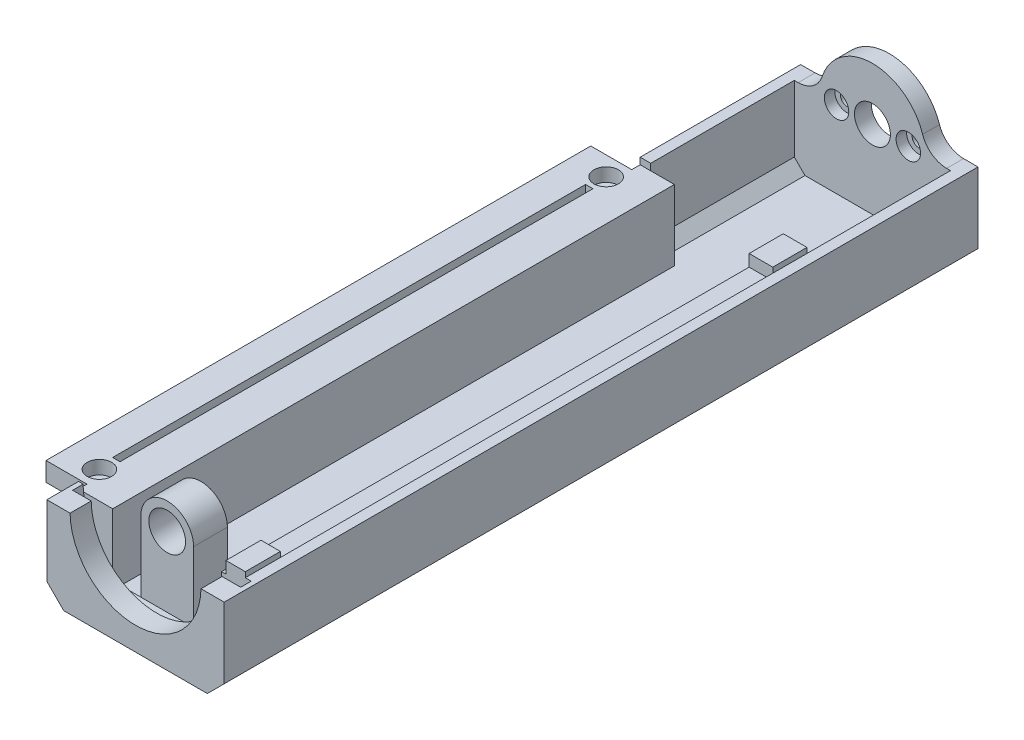
SolidWorks part; units mm, degrees
ref_plane "Front Plane" through (0, 0, 0) normal (0, 0, 1) x (1, 0, 0)
ref_plane "Top Plane" through (0, 0, 0) normal (0, 1, 0) x (1, 0, 0)
ref_plane "Right Plane" through (0, 0, 0) normal (1, 0, 0) x (0, 0, -1)
sketch "Sketch1" plane through (0, 0, 0) normal (0, 0, 1) x (1, 0, 0)
  line L0 (-21, -0.25) -> (21, -0.25)
  line L1 (-21, 21) -> (21, 21) construction
  line L2 (-21, 21) -> (-21, -21) construction
  line L3 (-21, -21) -> (21, -21) construction
  line L4 (21, 21) -> (21, -21) construction
  line L5 (-21, 21) -> (21, -21) construction
  line L6 (-21, -21) -> (21, 21) construction
  line L7 (21, -0.25) -> (21, -17)
  line L8 (21, -17) -> (17, -21)
  line L9 (17, -21) -> (-17, -21)
  line L10 (-17, -21) -> (-21, -17)
  line L11 (-21, -17) -> (-21, -0.25)
  point P0 (0, 0)
  dimension "D1" = 42
  dimension "D2" = 0.25
  dimension "D3" = 4
  dimension "D4" = 4
  dimension "D5" = 4
extrude "Boss-Extrude1" add sketch "Sketch1" along normal blind 178.5 contours L11 L0 L7 L8 L9 L10
ref_plane "Plane1" through (0, 0, 173.5) normal (0, 0, 1) x (1, 0, 0)
sketch "Sketch4" plane through (0, 0, 173.5) normal (0, 0, 1) x (1, 0, 0)
  line L6 (-18.5, -15.9645) -> (-15.9645, -18.5)
  line L7 (-15.9645, -18.5) -> (15.9645, -18.5)
  line L8 (15.9645, -18.5) -> (18.5, -15.9645)
  line L9 (18.5, -15.9645) -> (18.5, -2.75)
  line L11 (-18.5, -2.75) -> (-18.5, -15.9645)
  line L18 (-21, -17) -> (-17, -21)
  line L22 (-21, -0.25) -> (-21, -17)
  line L23 (21, -0.25) -> (-21, -0.25)
  line L24 (21, -17) -> (21, -0.25)
  line L25 (17, -21) -> (21, -17)
  line L26 (-17, -21) -> (17, -21)
  line L27 (-21, -17) -> (-17, -21) construction
  line L28 (-21, -0.25) -> (-21, -17) construction
  line L29 (21, -0.25) -> (-21, -0.25) construction
  line L30 (21, -17) -> (21, -0.25) construction
  line L31 (17, -21) -> (21, -17) construction
  line L32 (-17, -21) -> (17, -21) construction
  line L33 (-18.5, -2.75) -> (-18.5, -0.25)
  line L34 (-18.5, -0.25) -> (18.5, -0.25)
  line L35 (18.5, -0.25) -> (18.5, -2.75)
  line L39 (18.5, -2.75) -> (-18.5, -2.75) construction
  dimension "D1" = 0
  dimension "D2" = 2.5
extrude "Cut-Extrude3" cut sketch "Sketch4" against normal offset from surface (169.5 mm away) 4 up to face at (0, -12.75, 0)
sketch "Sketch3" plane through (0, 0, 178.5) normal (0, 0, 1) x (1, 0, 0)
  circle A0 centre (0, 0) radius 15.5
  dimension "D1" = 31
extrude "Cut-Extrude2" cut sketch "Sketch3" against normal up to next
sketch "Sketch6" plane through (0, 0, 173.5) normal (0, 0, 1) x (1, 0, 0)
  line L1 (-16.6, 16.6) -> (16.6, 16.6) construction
  line L2 (-16.6, 16.6) -> (-16.6, -16.6) construction
  line L3 (-16.6, -16.6) -> (16.6, -16.6) construction
  line L4 (16.6, 16.6) -> (16.6, -16.6) construction
  line L5 (-16.6, 16.6) -> (16.6, -16.6) construction
  line L6 (-16.6, -16.6) -> (16.6, 16.6) construction
  line L8 (-10.975, 16.6) -> (10.975, 16.6)
  line L9 (0, 0) -> (0, 16.6) construction
  line L20 (10.975, -16.6) -> (-10.975, -16.6)
  arc A13 (-10.975, 16.6) -> (-10.975, -16.6) centre (0, 0) ccw
  arc A14 (10.975, -16.6) -> (10.975, 16.6) centre (0, 0) ccw
  point P0 (0, 0)
  dimension "D1" = 39.8
  dimension "D2" = 33.2
extrude "Cut-Extrude4" cut sketch "Sketch6" against normal blind 2.5
ref_plane "Plane2" through (0, 0, 171) normal (0, 0, 1) x (1, 0, 0)
sketch "Sketch7" plane through (0, 0, 171) normal (0, 0, 1) x (1, 0, 0)
  line L1 (-6.25, 0) -> (-6.25, -21)
  line L2 (-6.25, -21) -> (6.25, -21)
  line L3 (6.25, -21) -> (6.25, 0)
  line L6 (17, -21) -> (-17, -21) construction
  arc A4 (-6.25, 0) -> (6.25, 0) centre (0, 0) cw
  circle A5 centre (0, 0) radius 4.25
  dimension "D2" = 6.25
  dimension "D1" = 8.5
extrude "Boss-Extrude3" add sketch "Sketch7" against normal blind 8 contours L3 A4 L1 L2
sketch "Sketch10" plane through (0, 0, 171) normal (0, 0, 1) x (1, 0, 0)
  line L0 (-18.5, -1.8) -> (-18.5, -15.9645)
  line L1 (-12.3089, -1.5) -> (-25.925, -1.5) construction
  line L2 (-18.5, -15.9645) -> (-15.9645, -18.5)
  line L3 (-15.9645, -18.5) -> (-12.9, -18.5)
  line L5 (-12.9, -18.5) -> (-12.9, -1.8)
  line L6 (-18.5, -1.8) -> (-12.9, -1.8)
  dimension "D1" = 0.3
  dimension "D2" = 0.5
extrude "Boss-Extrude4" add sketch "Sketch10" against normal blind 133 contours L6 L5 L3 L2 L0
mirror "Mirror1" about plane through (0, 0, 0) normal (1, 0, 0) of "Boss-Extrude4"
sketch "Sketch11" plane through (0, 0, 171) normal (0, 0, 1) x (1, 0, 0)
  circle A0 centre (0, 0) radius 4.35
  dimension "D1" = 8.7
extrude "Cut-Extrude6" cut sketch "Sketch11" against normal blind 10
sketch "Sketch12" plane through (0, 0, 38) normal (0, 0, -1) x (-1, 0, 0)
  line L1 (18.5, -1.8) -> (25.3381, -1.8)
  line L2 (18.5, -1.8) -> (18.5, 0)
  line L3 (18.5, 0) -> (25.3381, 0)
  line L4 (25.3381, -1.8) -> (25.3381, 0)
extrude "Cut-Extrude7" cut sketch "Sketch12" against normal up to vertex (133 mm away) up to point (-18.5, -0.25, 171)
sketch "Sketch13" plane through (0, -1.8, 0) normal (0, 1, 0) x (1, 0, 0)
  line L0 (-18.5, -38) -> (-12.9, -38) construction
  line L1 (-12.9, -40) -> (-30.7, -40)
  line L2 (-12.9, -40) -> (-12.9, -169)
  line L3 (-12.9, -169) -> (-30.7, -169)
  line L4 (-30.7, -40) -> (-30.7, -169)
  line L5 (-12.9, -38) -> (-12.9, -171) construction
  dimension "D1" = 129
  dimension "D2" = 17.8
  dimension "D3" = 2
extrude "Boss-Extrude5" add sketch "Sketch13" against normal blind 4.5
sketch "Sketch16" plane through (0, -6.3, 0) normal (0, -1, 0) x (1, 0, 0)
  line L2 (-30.7, 169) -> (-21, 169) construction
  line L3 (-30.7, 40) -> (-14.4, 40)
  line L4 (-30.7, 40) -> (-30.7, 169)
  line L5 (-30.7, 169) -> (-14.4, 169)
  line L6 (-14.4, 40) -> (-14.4, 169)
  dimension "D1" = 16.3
extrude "Cut-Extrude8" cut sketch "Sketch16" along normal through all
sketch "Sketch17" plane through (0, -6.3, 0) normal (0, -1, 0) x (1, 0, 0)
  line L0 (-22.55, 40) -> (-22.55, 169) construction
  line L1 (-30.7, 40) -> (-14.4, 40) construction
  line L2 (-30.7, 169) -> (-21, 169) construction
  line L3 (-22.55, 104.5) -> (-30.7, 104.5) construction
  line L4 (-21.675, 48.5) -> (-23.425, 48.5)
  line L5 (-21.675, 48.5) -> (-21.675, 160.5)
  line L6 (-21.675, 160.5) -> (-23.425, 160.5)
  line L7 (-23.425, 48.5) -> (-23.425, 160.5)
  line L8 (-21.675, 48.5) -> (-23.425, 160.5) construction
  line L9 (-21.675, 160.5) -> (-23.425, 48.5) construction
  line L10 (-30.7, 40) -> (-30.7, 169) construction
  circle A0 centre (-22.55, 164.5) radius 1.6
  circle A1 centre (-22.55, 44.5) radius 1.6
  point P7 (-22.55, 104.5)
  point P8 (-22.55, 40)
  dimension "D3" = 3.2
  dimension "D1" = 112
  dimension "D2" = 1.75
  dimension "D4" = 60
extrude "Cut-Extrude10" cut sketch "Sketch17" against normal through all
sketch "Sketch18" plane through (0, -1.8, 0) normal (0, 1, 0) x (1, 0, 0)
  circle A0 centre (-22.55, -164.5) radius 2.9
  circle A1 centre (-22.55, -44.5) radius 2.9
  dimension "D1" = 5.8
extrude "Cut-Extrude11" cut sketch "Sketch18" against normal blind 3.2
sketch "Sketch19" plane through (0, 0, 0) normal (0, 0, 1) x (1, 0, 0)
  circle A0 centre (0, 0) radius 12.5
  dimension "D1" = 25
extrude "Boss-Extrude6" add sketch "Sketch19" along normal blind 4 contours A0
sketch "Sketch20" plane through (0, 0, 0) normal (0, 0, 1) x (1, 0, 0)
  line L0 (-21, 21) -> (21, -21) construction
  line L1 (-21, -0.25) -> (21, -0.25) construction
  line L2 (0, 0) -> (0, 12.5) construction
  circle A0 centre (0, 0) radius 4.25
  circle A1 centre (-8.5, -0.25) radius 1.6
  arc A2 (12.4975, -0.25) -> (-12.4975, -0.25) centre (0, 0) ccw construction
  circle A3 centre (8.5, -0.25) radius 1.6
  dimension "D1" = 8.5
  dimension "D2" = 3.2
  dimension "D3" = 8.5
extrude "Cut-Extrude12" cut sketch "Sketch20" along normal blind 4
sketch "Sketch21" plane through (0, 0, 4) normal (0, 0, 1) x (1, 0, 0)
  circle A0 centre (-8.5, -0.25) radius 2.9
  circle A1 centre (8.5, -0.25) radius 2.9
  dimension "D1" = 5.8
extrude "Cut-Extrude13" cut sketch "Sketch21" against normal blind 2.5
fillet "Fillet1" radius 6 2 edges at (-12.4975, -0.25, 2) (12.4975, -0.25, 2)
sketch "Sketch22" plane through (0, -1.8, 0) normal (0, 1, 0) x (1, 0, 0)
  line L0 (18.5, -38) -> (18.5, -171) construction
  line L1 (12.9, -38) -> (18.5, -38)
  line L2 (12.9, -38) -> (12.9, -46.1)
  line L3 (12.9, -46.1) -> (18.5, -46.1)
  line L4 (18.5, -38) -> (18.5, -46.1)
  line L5 (18.5, -171) -> (12.9, -171) construction
  line L6 (18.5, -171) -> (13.9, -171)
  line L7 (18.5, -171) -> (18.5, -162.7)
  line L8 (18.5, -162.7) -> (13.9, -162.7)
  line L9 (13.9, -171) -> (13.9, -162.7)
  line L10 (12.9, -38) -> (12.9, -171) construction
  point P13 (14.3699, -171)
  point P14 (18.5, -171)
  dimension "D1" = 8.1
  dimension "D2" = 1
  dimension "D3" = 8.3
extrude "Boss-Extrude7" add sketch "Sketch22" along normal blind 2.8
sketch "Sketch23" plane through (0, 0, 173.5) normal (0, 0, -1) x (-1, 0, 0)
  line L0 (-10.975, -16.6) -> (10.975, -16.6) construction
  line L1 (-10.975, -16.6) -> (10.975, -16.6)
  line L2 (18.5, -7.3321) -> (-18.5, -7.3321) construction
  line L4 (-18.5, -15.9645) -> (-18.5, -7.3321) construction
  line L5 (-15.9645, -18.5) -> (-18.5, -15.9645) construction
  line L6 (15.9645, -18.5) -> (-15.9645, -18.5) construction
  line L7 (18.5, -15.9645) -> (15.9645, -18.5) construction
  line L8 (18.5, -7.3321) -> (18.5, -15.9645) construction
  line L9 (-18.5, -15.9645) -> (-18.5, -7.3321)
  line L10 (-15.9645, -18.5) -> (-18.5, -15.9645)
  line L11 (15.9645, -18.5) -> (-15.9645, -18.5)
  line L12 (18.5, -15.9645) -> (15.9645, -18.5)
  line L13 (18.5, -7.3321) -> (18.5, -15.9645)
  arc A0 (-10.975, 16.6) -> (-10.975, -16.6) centre (0, 0) ccw construction
  arc A1 (10.975, -16.6) -> (10.975, 16.6) centre (0, 0) ccw construction
  arc A2 (-18.5, -7.3321) -> (-10.975, -16.6) centre (0, 0) ccw
  arc A3 (10.975, -16.6) -> (18.5, -7.3321) centre (0, 0) ccw
  point P4 (0, 0)
  point P6 (10.975, -16.6)
  point P8 (0, 0)
  point P11 (18.5, -5.5183)
  point P14 (0, 0)
extrude "Boss-Extrude8" add sketch "Sketch23" along normal up to surface (2.5 mm away) up to plane "Plane2"
